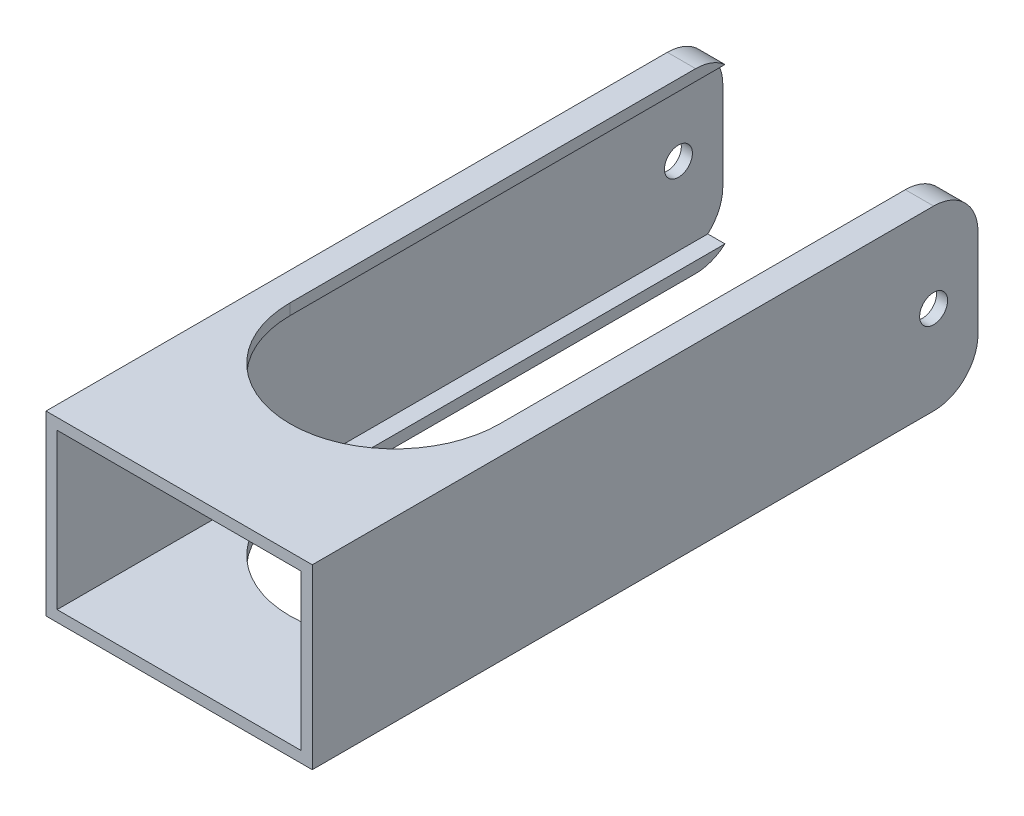
SolidWorks part; units mm, degrees
ref_plane "Front Plane" through (0, 0, 0) normal (0, 0, 1) x (1, 0, 0)
ref_plane "Top Plane" through (0, 0, 0) normal (0, 1, 0) x (1, 0, 0)
ref_plane "Right Plane" through (0, 0, 0) normal (1, 0, 0) x (0, 0, -1)
sketch "Sketch1" plane through (0, 0, 0) normal (0, 0, 1) x (1, 0, 0)
  line L0 (38.1, 0) -> (34.925, 0) construction
  line L1 (-38.1, 0) -> (38.1, 0) construction
  line L2 (0, 25.4) -> (0, -25.4)
  point P7 (0, 0)
sketch "Sketch2" plane through (0, 0, 0) normal (1, 0, 0) x (0, 0, -1)
  line L0 (95.25, 0) -> (-95.25, 0)
  point P4 (0, 0)
  dimension "Length" = 190.5
sketch "Sketch3" plane through (0, 0, 0) normal (0, 0, 1) x (1, 0, 0)
  line L0 (-38.1, 0) -> (38.1, 0) construction
  line L5 (38.1, -25.4) -> (-38.1, -25.4)
  line L6 (38.1, -25.4) -> (38.1, 25.4)
  line L11 (38.1, 25.4) -> (-38.1, 25.4)
  line L12 (-38.1, -25.4) -> (-38.1, 25.4)
  line L14 (38.1, -25.4) -> (-38.1, 25.4) construction
  line L15 (38.1, 25.4) -> (-38.1, -25.4) construction
  line L16 (34.925, -22.225) -> (-34.925, -22.225)
  line L17 (34.925, -22.225) -> (34.925, 22.225)
  line L18 (34.925, 22.225) -> (-34.925, 22.225)
  line L19 (-34.925, -22.225) -> (-34.925, 22.225)
  line L20 (34.925, -22.225) -> (-34.925, 22.225) construction
  line L21 (34.925, 22.225) -> (-34.925, -22.225) construction
  point P0 (0, 0)
  point P5 (0, 0)
  point P13 (34.925, -25.4)
  dimension "D1" = 3.175
  dimension "D3" = 76.2
  dimension "D4" = 50.8
  dimension "D2" = 3.175
extrude "Boss-Extrude1" add sketch "Sketch3" along normal up to vertex (95.25 mm away) and the other way up to vertex (95.25 mm away) up to point (0, 0, 95.25) other way up to point (0, 0, -95.25)
sketch "Sketch5" plane through (0, 0, 0) normal (1, 0, 0) x (0, 0, -1)
  line L0 (-95.25, 0) -> (95.25, 0) construction
  line L3 (-95.25, -25.4) -> (-95.25, 25.4) construction
  line L4 (95.25, -25.4) -> (95.25, 25.4) construction
  point P6 (-9.525, 0)
  point P7 (19.05, 0)
  point P8 (-19.05, 0)
  point P10 (9.525, 0)
  dimension "D1" = 85.725
  dimension "D2" = 114.3
  dimension "D3" = 85.725
  dimension "D4" = 114.3
sketch "Sketch6" plane through (0, 25.4, 0) normal (0, 1, 0) x (1, 0, 0)
  line L0 (-30, 95.25) -> (-30, -33.5)
  line L1 (38.1, 95.25) -> (-38.1, 95.25) construction
  line L2 (30, 95.25) -> (30, -33.5)
  line L3 (38.1, -95.25) -> (-38.1, -95.25) construction
  arc A0 (-30, -33.5) -> (30, -33.5) centre (0, -33.5) ccw
  point P9 (0, 0)
  line M4 (38.1, 95.25) -> (-38.1, 95.25)
  dimension "D1" = 31.75
  dimension "D2" = 60
extrude "Cut-Extrude1" cut sketch "Sketch6" against normal through all and the other way through all contours L0 A0 L2 M4 region at (0, 25.4, -18.9468)
sketch "Sketch7" plane through (38.1, 0, 0) normal (1, 0, 0) x (0, 0, -1)
  line L2 (95.25, -25.4) -> (95.25, 25.4) construction
  circle A0 centre (82.55, 0) radius 4
  dimension "D1" = 8
  dimension "D2" = 12.7
extrude "Cut-Extrude2" cut sketch "Sketch7" against normal through all
fillet "Fillet1" radius 12.7 4 edges at (-34.05, -25.4, -95.25) (-34.05, 25.4, -95.25) (34.05, -25.4, -95.25) (34.05, 25.4, -95.25)
equation "\"D1@Sketch3\"=\"Wall thickness@Sketch1\""
equation "\"D1@Sketch5\"=\"Width@Sketch1\"*1.125"
equation "\"D2@Sketch5\"=\"Width@Sketch1\"*1.5"
equation "\"D3@Sketch5\"=\"D1@Sketch5\""
equation "\"D4@Sketch5\"=\"D2@Sketch5\""
equation "\"D2@Sketch3\"=\"Wall Thickness@Sketch1\""
